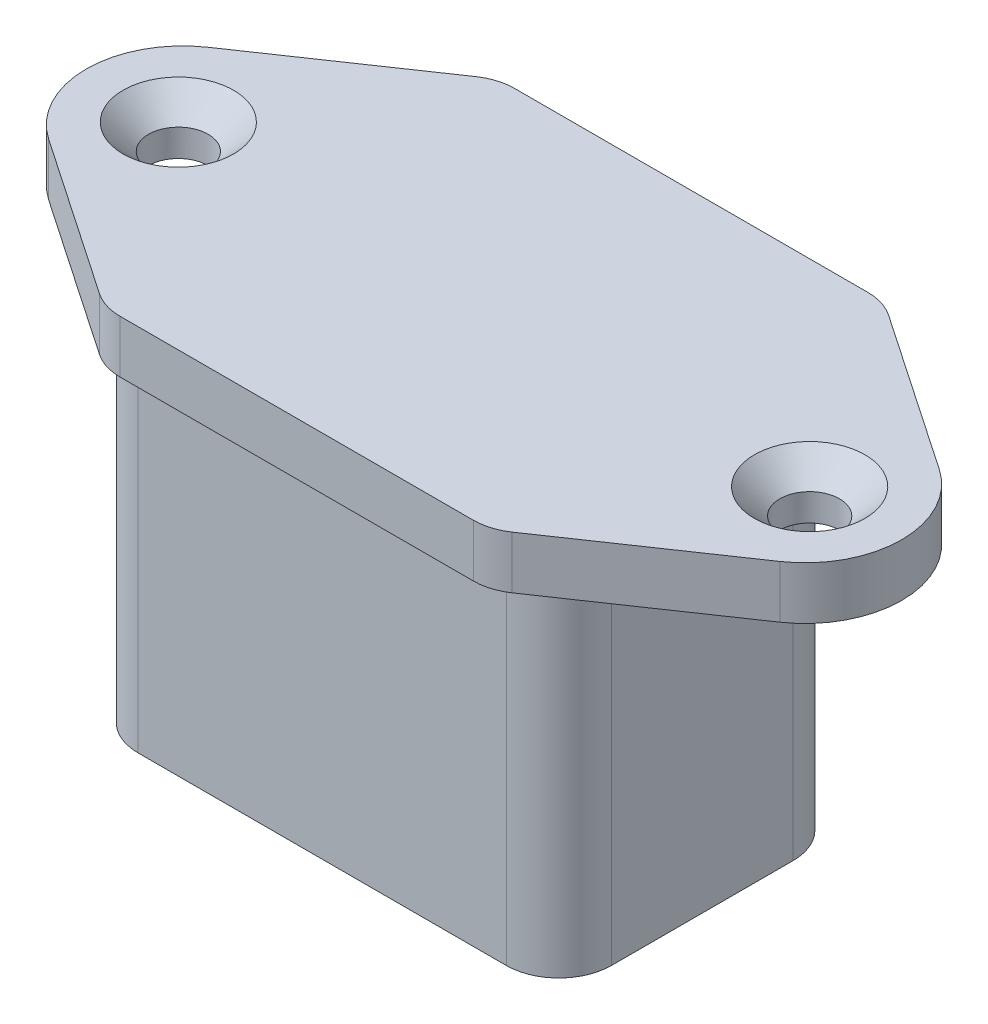
SolidWorks part; units mm, degrees
ref_plane "Ebene vorne" through (0, 0, 0) normal (0, 0, 1) x (1, 0, 0)
ref_plane "Ebene oben" through (0, 0, 0) normal (0, 1, 0) x (1, 0, 0)
ref_plane "Ebene rechts" through (0, 0, 0) normal (1, 0, 0) x (0, 0, -1)
sketch "Skizze1" plane through (0, 0, 0) normal (0, 0, 1) x (1, 0, 0)
  line L1 (-13.5, -9.75) -> (13.5, -9.75)
  line L2 (-13.5, -9.75) -> (-13.5, 9.75)
  line L3 (-13.5, 9.75) -> (13.5, 9.75)
  line L4 (13.5, -9.75) -> (13.5, 9.75)
  line L5 (-13.5, -9.75) -> (13.5, 9.75) construction
  line L6 (-13.5, 9.75) -> (13.5, -9.75) construction
  point P0 (0, 0)
  dimension "D1" = 19.5
  dimension "D2" = 27
extrude "Aufsatz-Linear austragen1" add sketch "Skizze1" along normal blind 19.6
chamfer "Fase1" distance 5 angle 45 2 edges at (13.5, 0, 0) (-13.5, 0, 0)
sketch "Skizze2" plane through (0, 9.75, 0) normal (0, 1, 0) x (1, 0, 0)
  line L0 (0, 0) -> (0, -19.6) construction
  line L1 (8.5, 0) -> (-8.5, 0) construction
  line L2 (0, 0) -> (0, 1.45) construction
  line L3 (13.5, -19.6) -> (-13.5, -19.6) construction
  line L4 (0, -9.8) -> (23.25, -9.8) construction
  line L5 (-11, 1.45) -> (11, 1.45)
  line L6 (11, 1.45) -> (20.8455, -5.2538)
  line L7 (11, -21.05) -> (20.8455, -14.3462)
  line L8 (-11, -21.05) -> (11, -21.05)
  line L9 (-11, 1.45) -> (-20.8455, -5.2538)
  line L10 (-11, -21.05) -> (-20.8455, -14.3462)
  arc A0 (20.8455, -5.2538) -> (20.8455, -14.3462) centre (17.75, -9.8) cw
  arc A1 (-20.8455, -5.2538) -> (-20.8455, -14.3462) centre (-17.75, -9.8) ccw
  point P22 (0, -21.05)
  dimension "D2" = 5.5
  dimension "D1" = 22.5
  dimension "D3" = 11
  dimension "D4" = 46.5
extrude "Aufsatz-Linear austragen2" add sketch "Skizze2" along normal blind 3
fillet "Verrundung1" radius 3 10 edges at (11, 11.25, 21.05) (-11, 11.25, 21.05) (-11, 11.25, -1.45) (11, 11.25, -1.45) (13.5, 0, 5) (8.5, 0, 0) (-8.5, 0, 0) (-13.5, 0, 5) (-13.5, 0, 19.6) (13.5, 0, 19.6)
hole_wizard "Formsenkung für M3 Linsensenkschraube mit Schlitz1" positions "Skizze3" profile "Skizze4" countersink size "M3" standard "DIN" end condition up to next
sketch "Skizze3" plane through (0, 12.75, 0) normal (0, 1, 0) x (1, 0, 0)
  line L0 (0, 1.45) -> (0, -21.05) construction
  line L1 (10.0756, 1.45) -> (-10.0756, 1.45) construction
  line L2 (-10.0756, -21.05) -> (10.0756, -21.05) construction
  line L4 (-18, -9.8) -> (0, -9.8) construction
  line L5 (0, -9.8) -> (18, -9.8) construction
  point P0 (-18, -9.8)
  point P2 (18, -9.8)
  dimension "D1" = 36
sketch "Skizze4" plane through (-18, 12.75, 9.8) normal (1, 0, 0) x (0, 0, 1)
  line L0 (0, 0) -> (0, 3)
  line L1 (0, 3) -> (1.7, 3)
  line L2 (1.7, 3) -> (1.7, 1.45)
  line L3 (1.7, 1.45) -> (3.15, 0)
  line L5 (3.15, 0) -> (0, 0)
  line L6 (-1.7, 1.45) -> (-3.15, 0) construction
  line L11 (0, -6.35) -> (0, 107.95) construction
  dimension "Bohrerdurchmesser" = 3.4
  dimension "Bohrungstiefe" = 3
  dimension "Senkdurchmesser (Oben)" = 6.3
  dimension "Senkwinkel (Oben)" = 90
